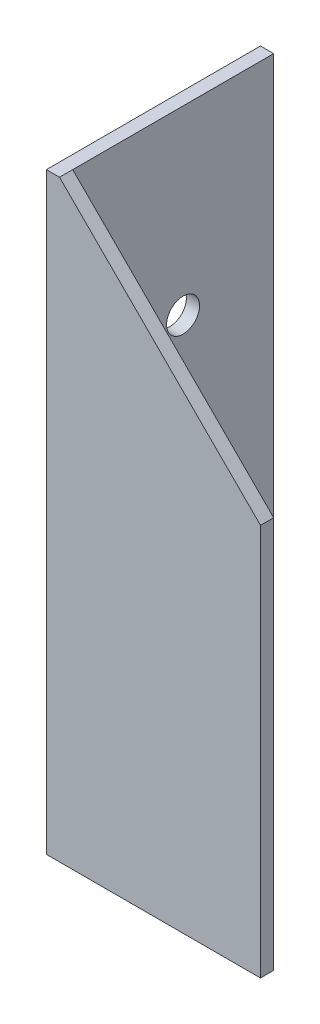
SolidWorks part; units mm, degrees
ref_plane "Спереди" through (0, 0, 0) normal (0, 0, 1) x (1, 0, 0)
ref_plane "Сверху" through (0, 0, 0) normal (0, 1, 0) x (1, 0, 0)
ref_plane "Справа" through (0, 0, 0) normal (1, 0, 0) x (0, 0, -1)
sketch "Эскиз1" plane through (0, 0, 0) normal (0, 1, 0) x (1, 0, 0)
  line L0 (0, 0) -> (65, 0)
  line L1 (0, 0) -> (0, 65)
extrude "Вытянуть-Тонкостенный1" add sketch "Эскиз1" along normal blind 180 thin thin type one direction wall 4
sketch "Эскиз6" plane through (0, 0, 0) normal (-1, 0, 0) x (0, 0, 1)
  circle A0 centre (-37.5, 25) radius 5
  circle A1 centre (-37.5, 75) radius 5
  circle A2 centre (-37.5, 125) radius 5
  dimension "D1" = 3
extrude "Вырез-Вытянуть1" cut sketch "Эскиз6" against normal blind 10
sketch "Эскиз7" plane through (0, 0, 0) normal (0, 0, 1) x (1, 0, 0)
  line L0 (4, 180) -> (65, 180)
  line L1 (65, 180) -> (0, 180) construction
  line L2 (65, 119) -> (65, 180)
  line L3 (65, 180) -> (65, 0) construction
  line L4 (4, 180) -> (65, 119)
extrude "Вырез-Вытянуть2" cut sketch "Эскиз7" against normal blind 10
